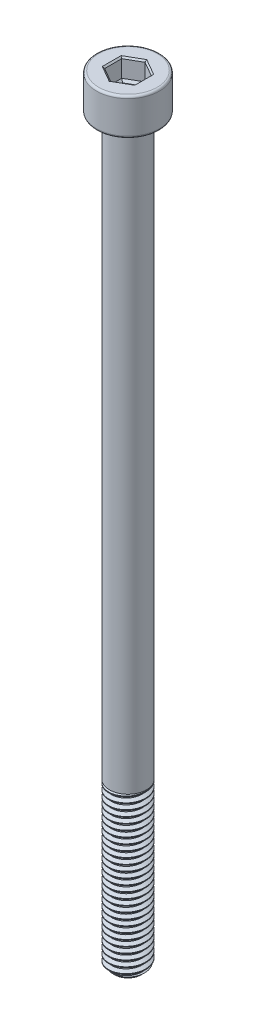
SolidWorks part; units mm, degrees
material "AISI Type A2 Tool Steel"
ref_plane "Front Plane" through (0, 0, 0) normal (0, 0, 1) x (1, 0, 0)
ref_plane "Top Plane" through (0, 0, 0) normal (0, 1, 0) x (1, 0, 0)
ref_plane "Right Plane" through (0, 0, 0) normal (1, 0, 0) x (0, 0, -1)
sketch "Sketch1" plane through (0, 0, 0) normal (0, 1, 0) x (1, 0, 0)
  circle A0 centre (0, 0) radius 2.5
  dimension "D1" = 5
extrude "Boss-Extrude1" add sketch "Sketch1" along normal blind 22
thread "Thread1" pitch 0.8 method cut profile "Thread Profile1" start angle 0, offset 1, length 0, pitch 0.8, diameter 5
ref_plane "Plane1" through (-2.5, 23, 0) normal (0, 0, 1) x (-1, 0, 0)
sketch "Thread Profile1" plane through (-2.5, 23, 0) normal (0, 0, 1) x (-1, 0, 0)
  line L0 (0, 0) -> (0, 0.8) construction
  line L11 (0, 0) -> (0, 0.7)
  line L12 (0, 0.7) -> (-0.433, 0.45)
  line L13 (-0.433, 0.45) -> (-0.433, 0.25)
  line L15 (-0.433, 0.25) -> (0, 0)
  line L17 (-0.433, 0.35) -> (0, 0.35) construction
  point P2 (0, 0)
  dimension "Pitch" = 0.8
  dimension "Profile_Angle" = 60
  dimension "Profile_Land" = 0.2
  dimension "Profile_Height" = 0.433
sketch "Sketch2" plane through (0, 22, 0) normal (0, 1, 0) x (1, 0, 0)
  circle A0 centre (0, 0) radius 2.5
  dimension "D1" = 5
extrude "Boss-Extrude2" add sketch "Sketch2" along normal blind 78
sketch "Sketch3" plane through (0, 100, 0) normal (0, 1, 0) x (1, 0, 0)
  circle A0 centre (0, 0) radius 4.25
  dimension "D1" = 8.5
extrude "Boss-Extrude3" add sketch "Sketch3" along normal blind 5
fillet "Fillet1" radius 0.3 2 edges at (0, 100, 4.25) (0, 105, 4.25)
sketch "Sketch4" plane through (0, 0, 0) normal (0, 0, 1) x (1, 0, 0)
  line L0 (0, 0) -> (0, 0.4416) construction
  line L1 (0, 0) -> (2.51, 0) construction
  line L2 (2.51, 0) -> (2.51, 0.7)
  line L3 (2.51, 0.7) -> (1.81, 0)
  line L4 (1.81, 0) -> (2.51, 0)
  dimension "D1" = 0.7
  dimension "D2" = 45
  dimension "D3" = 2.51
revolve "Cut-Revolve1" cut sketch "Sketch4" angle 360 about L0
sketch "Sketch5" plane through (0, 105, 0) normal (0, 1, 0) x (1, 0, 0)
  line L1 (0, 2.3094) -> (-2, 1.1547)
  line L2 (-2, 1.1547) -> (-2, -1.1547)
  line L3 (-2, -1.1547) -> (0, -2.3094)
  line L4 (0, -2.3094) -> (2, -1.1547)
  line L5 (2, -1.1547) -> (2, 1.1547)
  line L6 (2, 1.1547) -> (0, 2.3094)
  circle A0 centre (0, 0) radius 2 construction
  dimension "D1" = 4
extrude "Cut-Extrude1" cut sketch "Sketch5" against normal blind 2.5
chamfer "Chamfer1" distance 0.2 angle 45 6 edges at (-1, 105, 1.7321) (1, 105, 1.7321) (2, 105, 0) (1, 105, -1.7321) (-1, 105, -1.7321) (-2, 105, 0)
sketch "Sketch6" plane through (0, 102.5, 0) normal (0, 1, 0) x (1, 0, 0)
  line L1 (0, 2.3094) -> (-2, 1.1547)
  line L2 (-2, 1.1547) -> (-2, -1.1547)
  line L3 (-2, -1.1547) -> (0, -2.3094)
  line L4 (0, -2.3094) -> (2, -1.1547)
  line L5 (2, -1.1547) -> (2, 1.1547)
  line L6 (2, 1.1547) -> (0, 2.3094)
  circle A0 centre (0, 0) radius 2 construction
extrude "Cut-Extrude2" cut sketch "Sketch6" against normal blind 0.3 draft 45
